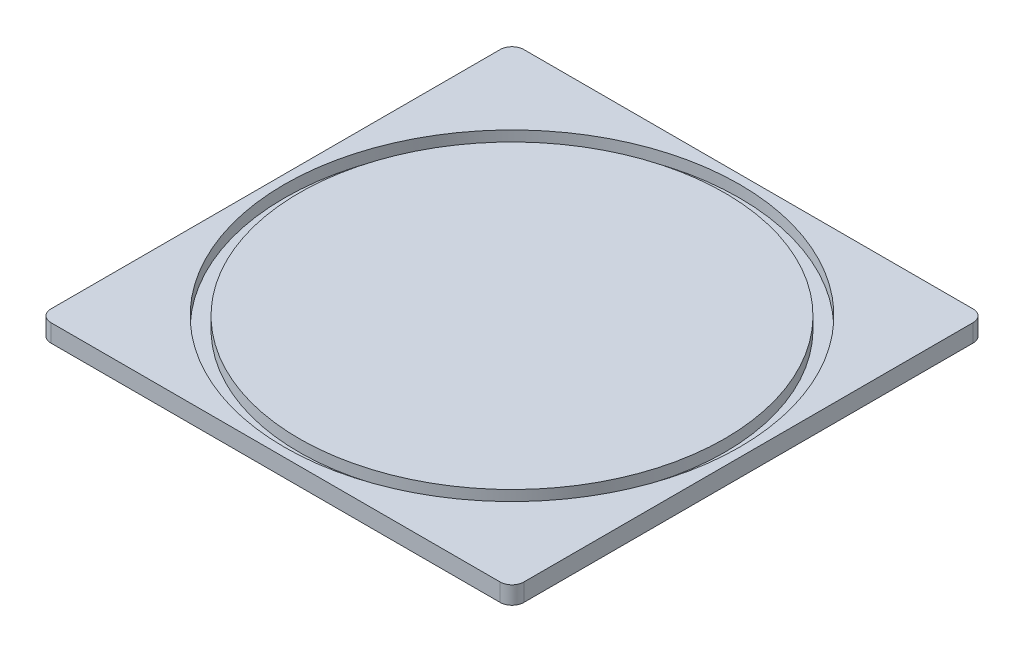
SolidWorks part; units mm, degrees
ref_plane "Front Plane" through (0, 0, 0) normal (0, 0, 1) x (1, 0, 0)
ref_plane "Top Plane" through (0, 0, 0) normal (0, 1, 0) x (1, 0, 0)
ref_plane "Right Plane" through (0, 0, 0) normal (1, 0, 0) x (0, 0, -1)
sketch "Sketch1" plane through (0, 0, 0) normal (0, 1, 0) x (1, 0, 0)
  line L0 (0, 40) -> (0, -40)
  line L1 (0, -40) -> (80, -40)
  line L2 (80, -40) -> (80, 40)
  line L3 (80, 40) -> (0, 40)
  dimension "D1" = 40
  dimension "D2" = 80
  dimension "D3" = 80
extrude "Boss-Extrude1" add sketch "Sketch1" along normal blind 3
sketch "Sketch3" plane through (0, 3, 0) normal (0, 1, 0) x (1, 0, 0)
  line L4 (80, -40) -> (80, 40) construction
  line L5 (0, -40) -> (80, -40) construction
  circle A0 centre (40, 0) radius 38.5
  dimension "D3" = 77
  dimension "D1" = 40
  dimension "D2" = 40
extrude "Cut-Extrude-Thin1" cut sketch "Sketch3" against normal blind 2 thin thin type one direction reverse wall 2.5
fillet "Fillet1" radius 2 4 edges at (0, 1.5, -40) (0, 1.5, 40) (80, 1.5, -40) (80, 1.5, 40)
